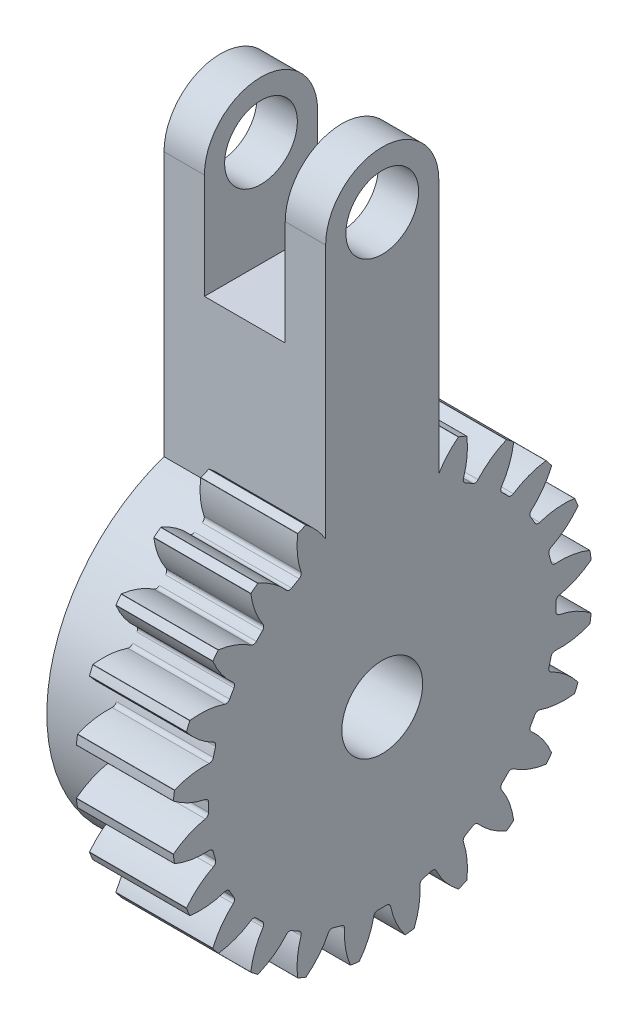
SolidWorks part; units mm, degrees
material "Nylon 101"
ref_plane "Plane1" through (0, 0, 0) normal (0, 0, 1) x (1, 0, 0)
ref_plane "Plane2" through (0, 0, 0) normal (0, 1, 0) x (1, 0, 0)
ref_plane "Plane3" through (0, 0, 0) normal (1, 0, 0) x (0, 0, -1)
sketch "HoldingSke" plane through (0, 0, 0) normal (0, 1, 0) x (1, 0, 0)
  line L0 (0, 0) -> (0.9135, -0.4067)
  line L1 (-15, 0) -> (100, 0) construction
  line L2 (0, 0) -> (-2.1039, 2.3779)
  line L3 (0, 0) -> (-11.863, 4.5341)
  line L4 (0, 0) -> (7.8894, 3.5126)
  line L5 (0, 0) -> (-46.8476, -17.4728)
  line L6 (0, 0) -> (-4.9738, -3.3558)
  line L7 (-2.1039, 2.3779) -> (8.6589, 51.2071)
  line L8 (-76.2, 54.61) -> (-75.5, 54.61)
  line L9 (-71.009, 38.7566) -> (-53.1078, 45.2721)
  line L10 (-76.2, 71.12) -> (104.1128, 71.12)
  line L11 (0, 0) -> (-6, 0)
  line L12 (-76.2, 101.6) -> (-76.162, 101.6)
  line L13 (24.9733, 27.94) -> (52.9518, 28.4284)
  line L14 (24.9733, 27.94) -> (24.9743, 27.94)
  line L15 (24.9733, 27.94) -> (100.4006, 29.5858)
  line L16 (-63.627, -1) -> (-12.827, -1)
  circle A0 centre (0, 0) radius 2
  circle A1 centre (0, 0) radius 10.749
  circle A2 centre (0, 0) radius 37.5
  circle A3 centre (0, 0) radius 2
  dimension "Num_teeth" = 24
  dimension "Pitch_radius" = 180.3128
  dimension "Width" = 6
  dimension "Thickness" = 6
sketch "BasProSke" plane through (0, 0, 0) normal (0, 1, 0) x (1, 0, 0)
  line L0 (-10, 0) -> (60, 0) construction
  line L1 (0, 0) -> (0, 13)
  line L2 (0, 0) -> (6, 0)
  line L3 (6, 0) -> (6, 13)
  line L4 (6, 13) -> (0, 13)
  dimension "Thickness" = 6
  dimension "Diameter" = 26
revolve "Base-Revolve" add sketch "BasProSke" angle 360 about L0
sketch "TooCutSke" plane through (0, 0, 0) normal (1, 0, 0) x (0, 0, -1)
  line L1 (0, 0) -> (0, 107) construction
  line L2 (0, 0) -> (-0.8513, 11.9698) construction
  line L3 (0, 0) -> (-3.127, 23.752) construction
  line L4 (-0.8513, 11.9698) -> (-1.5635, 11.876) construction
  arc A0 (0.4834, 10.7381) -> (-0.4834, 10.7381) centre (0, 0) ccw
  arc A1 (1.4409, 12.9455) -> (-1.4409, 12.9455) centre (0, 0) ccw
  circle A2 centre (0, 0) radius 12 construction
  circle A3 centre (0, 0) radius 11.2763 construction
  arc A4 (-0.4834, 10.7381) -> (-1.4409, 12.9455) centre (-5.2252, 9.9926) ccw
  arc A5 (1.4409, 12.9455) -> (0.4834, 10.7381) centre (5.2252, 9.9926) ccw
extrude "ToothCut" cut sketch "TooCutSke" along normal through all
fillet "Breaks" radius 0.02 2 edges at (3, 12.9219, -1.4227) (3, 12.9219, 1.4227) tangent propagation no
fillet "RootFillets" radius 0.251 2 edges at (3, 10.7381, -0.4834) (3, 10.7381, 0.4834)
pattern_circular "TeethCuts" count 24 over 360 about axis through (-10, 0, 0) along (1, 0, 0) of "ToothCut", "RootFillets", "Breaks"
sketch "HubNeaOneSke" plane through (0, 0, 0) normal (-1, 0, 0) x (0, 0, 1)
  circle A0 centre (0, 0) radius 10.749
  dimension "Diameter" = 21.498
extrude "HubNearOne" add sketch "HubNeaOneSke" along normal blind 4
sketch "HubNeaBotSke" plane through (0, 0, 0) normal (-1, 0, 0) x (0, 0, 1)
  circle A0 centre (0, 0) radius 10.749
  dimension "Diameter" = 21.498
extrude "HubNearBoth" add sketch "HubNeaBotSke" along normal blind 4
sketch "BorSke" plane through (0, 0, 0) normal (1, 0, 0) x (0, 0, -1)
  circle A0 centre (0, 0) radius 2.5
  dimension "Diameter" = 5
extrude "Bore" cut sketch "BorSke" along normal mid plane 100.0025
ref_plane "FarPln" through (6, 0, 0) normal (1, 0, 0) x (0, 0, -1)
sketch "HubFarSke" plane through (6, 0, 0) normal (1, 0, 0) x (0, 0, -1)
  circle A0 centre (0, 0) radius 10.749
  dimension "Diameter" = 21.498
extrude "HubFar" [suppressed] add sketch "HubFarSke" along normal blind 22.0006
sketch "Эскиз1" plane through (0, 0, 0) normal (-1, 0, 0) x (0, 0, 1)
  circle A0 centre (0, 0) radius 9
  dimension "D1" = 18
extrude "Бобышка-Вытянуть1" add sketch "Эскиз1" along normal blind 4
sketch "Эскиз2" plane through (-4, 0, 0) normal (-1, 0, 0) x (0, 0, 1)
  circle A0 centre (0, 0) radius 2.5
  dimension "D1" = 5
extrude "Вырез-Вытянуть1" cut sketch "Эскиз2" against normal through all
sketch "Эскиз3" plane through (0, 0, 0) normal (1, 0, 0) x (0, 0, -1)
  line L0 (0, 0) -> (0, 30) construction
  line L1 (-3.5, 26.5) -> (-3.5, 7)
  line L2 (3.5, 26.5) -> (3.5, 7)
  line L4 (3.5, 7) -> (-3.5, 7)
  arc A0 (-3.5, 26.5) -> (3.5, 26.5) centre (0, 26.5) cw
  dimension "D4" = 7
  dimension "D3" = 3.5
  dimension "D1" = 30
  dimension "D2" = 26.5
extrude "Бобышка-Вытянуть2" add sketch "Эскиз3" along normal blind 6 and the other way blind 4
sketch "Эскиз4" plane through (0, 0, 0) normal (0, 0, 1) x (1, 0, 0)
  line L0 (-1.5, 32) -> (3.5, 32)
  line L1 (-1.5, 32) -> (-1.5, 20)
  line L2 (-1.5, 20) -> (3.5, 20)
  line L3 (3.5, 32) -> (3.5, 20)
  line L4 (0, 10.749) -> (0, -10.749) construction
  line L5 (-4, 30) -> (-4, 26.5) construction
  point P6 (0, 0)
  dimension "D1" = 12
  dimension "D2" = 5
  dimension "D3" = 20
  dimension "D4" = 2.5
extrude "Вырез-Вытянуть2" cut sketch "Эскиз4" against normal through all both and the other way through all
hole_wizard "Отверстие с зазором M41" positions "Эскиз7" profile "Эскиз6" hole size "M4" standard "JIS"
sketch "Эскиз7" plane through (6, 0, 0) normal (1, 0, 0) x (0, 0, -1)
  line L0 (3.5, 10.74) -> (3.5, 26.5) construction
  arc A1 (3.5, 26.5) -> (-3.5, 26.5) centre (0, 26.5) ccw construction
  point P0 (0, 26.5)
  point P17 (0, 30)
  dimension "D1" = 3.5
  dimension "D2" = 3.5
sketch "Эскиз6" plane through (6, 26.5, 0) normal (0, 1, 0) x (0, 0, -1)
  line L0 (0, 0) -> (0, 16.3519)
  line L1 (0, 16.3519) -> (2.25, 15)
  line L2 (2.25, 15) -> (2.25, 0)
  line L5 (2.25, 0) -> (0, 0)
  line L10 (0, 16.3519) -> (-2.25, 15) construction
  line L11 (0, -6.35) -> (0, 107.95) construction
  dimension "Диаметр отверстия" = 4.5
  dimension "Глубина отверстия" = 15
  dimension "Угол заточки сверла" = 118
equation "' \"Module@HoldingSke\" = 6.35"
equation "' \"Num_teeth@HoldingSke\" = 12"
equation "' \"Ap@HoldingSke\" =  20"
equation "' \"Ap@HoldingSke\" = 20"
equation "' \"Width@HoldingSke\" = 0.5 * 25.4"
equation "' \"Hub_dia@HoldingSke\"= 1 * 25.4"
equation "' \"Hub_dia@HoldingSke\" = 1 * 25.4"
equation "' \"Overall_len@HoldingSke\" = 1.0 * 25.4"
equation "' \"Bore@HoldingSke\" = 0.75 * 25.4"
equation "' \"T_dim@HoldingSke\" = 0.1 * 25.4"
equation "' \"Width@KeySke\" = 0.25 * 25.4"
equation "' \"Show_teeth@HoldingSke\" = 13"
equation "' \"Backlash@HoldingSke\" = 0.009 * 25.4"
equation "' \"Addendum_fac@HoldingSke\" = 1.0"
equation "' \"Dedendum_fac@HoldingSke\" = 1.25"
equation "' \"Dedendum_add@HoldingSke\" = 0.00005 * 25.4"
equation "' \"Clearance_fac@HoldingSke\" = 0.25"
equation "\"Pitch@HoldingSke\" = 1 / \"Module@HoldingSke\""
equation "\"Overcut_dia@TooCutSke\" = (\"Num_teeth@HoldingSke\" + 2 * \"Addendum_fac@HoldingSke\") / \"Pitch@HoldingSke\" + 0.002 * 25.4"
equation "\"Pitch_dia@TooCutSke\" = \"Num_teeth@HoldingSke\" / \"Pitch@HoldingSke\""
equation "\"Base_dia@TooCutSke\" = \"Num_teeth@HoldingSke\" / \"Pitch@HoldingSke\" * cos((\"Ap@HoldingSke\"  * 3.14159265 / 180))"
equation "\"Root_dia@TooCutSke\" = (\"Num_teeth@HoldingSke\" + 2) / \"Pitch@HoldingSke\" - 2 * (\"Addendum_fac@HoldingSke\" + \"Dedendum_fac@HoldingSke\") / \"Pitch@HoldingSke\" - \"Dedendum_add@HoldingSke\" * 2"
equation "\"Half_ang@TooCutSke\" = 180 / \"Num_teeth@HoldingSke\""
equation "\"Half_CT@TooCutSke\" = \"Num_teeth@HoldingSke\" / \"Pitch@HoldingSke\" * sin((3.14159265 / 2 / \"Num_teeth@HoldingSke\")) / 2 - 7 * \"Backlash@HoldingSke\" / 4"
equation "\"Flank_rad@TooCutSke\" = \"Num_teeth@HoldingSke\" / \"Pitch@HoldingSke\" / 5"
equation "\"Radius@RootFillets\" = \"Clearance_fac@HoldingSke\" / \"Pitch@HoldingSke\" + \"Dedendum_add@HoldingSke\""
equation "\"Break_rad@Breaks\" = 0.02 / \"Pitch@HoldingSke\""
equation "\"Thickness@HoldingSke\" = \"Width@HoldingSke\""
equation "\"OAL@HoldingSke\" = \"Thickness@HoldingSke\""
equation "\"MHD@HoldingSke\" = (\"Num_teeth@HoldingSke\" + 2) / \"Pitch@HoldingSke\" - 2 * (\"Addendum_fac@HoldingSke\" + \"Dedendum_fac@HoldingSke\")  / \"Pitch@HoldingSke\" - \"Dedendum_add@HoldingSke\" * 2"
equation "\"MBD@HoldingSke\" = (\"Num_teeth@HoldingSke\" + 2) / \"Pitch@HoldingSke\" - 2 * (\"Addendum_fac@HoldingSke\" + \"Dedendum_fac@HoldingSke\")  / \"Pitch@HoldingSke\" - \"Dedendum_add@HoldingSke\" * 2 - 0.002 * 25.4"
equation "\"MHD@HoldingSke\" = ((sgn( \"MHD@HoldingSke\" - \"Hub_dia@HoldingSke\" )-1)*( \"MHD@HoldingSke\" - \"Hub_dia@HoldingSke\" ))/-2+ \"Hub_dia@HoldingSke\""
equation "\"MBD@HoldingSke\" = ((sgn( \"MBD@HoldingSke\" - \"Bore@HoldingSke\" )-1)*( \"MBD@HoldingSke\" - \"Bore@HoldingSke\" ))/-2+ \"Bore@HoldingSke\""
equation "\"OAL@HoldingSke\" = ((sgn( \"OAL@HoldingSke\" - \"Overall_len@HoldingSke\" )+1)*( \"OAL@HoldingSke\" - \"Overall_len@HoldingSke\" ))/2 + \"Overall_len@HoldingSke\" + 0.000002 * 25.4"
equation "\"Num_teeth@TeethCuts\" = int( \"Show_teeth@HoldingSke\" ) + 1"
equation "\"Num_teeth@TeethCuts\" = ((sgn( \"Num_teeth@TeethCuts\" - \"Num_teeth@HoldingSke\" )-1)*( \"Num_teeth@TeethCuts\" - \"Num_teeth@HoldingSke\" ))/-2+ \"Num_teeth@HoldingSke\""
equation "\"Num_teeth@TeethCuts\" = ((sgn( \"Num_teeth@TeethCuts\" - 2.0)+1)*( \"Num_teeth@TeethCuts\" - 2.0))/2 +2.0"
equation "\"Angle@TeethCuts\" = 360.0 / \"Num_teeth@HoldingSke\""
equation "\"Diameter@BasProSke\" = (\"Num_teeth@HoldingSke\" + 2 * \"Addendum_fac@HoldingSke\") / \"Pitch@HoldingSke\""
equation "\"Thickness@BasProSke\"  = \"Thickness@HoldingSke\""
equation "' \"Fillet_rad@BasProSke\" =  \"Thickness@HoldingSke\" * 0.05"
equation "' \"Fillet_rad@BasProSke\" = \"Thickness@HoldingSke\" * 0.05"
equation "\"MHD@HoldingSke\" = ((sgn( \"MHD@HoldingSke\" - \"Root_dia@TooCutSke\" )-1)*( \"MHD@HoldingSke\" - \"Root_dia@TooCutSke\" ))/-2+ \"Root_dia@TooCutSke\""
equation "\"Diameter@HubNeaOneSke\" = \"MHD@HoldingSke\""
equation "\"Diameter@HubNeaBotSke\" = \"MHD@HoldingSke\""
equation "\"Thickness@FarPln\" = \"Thickness@BasProSke\""
equation "\"Diameter@HubFarSke\" = \"MHD@HoldingSke\""
equation "\"Length@HubFar\" = ( \"OAL@HoldingSke\" - \"Thickness@BasProSke\" ) / 2.0"
equation "\"D1@Bore\" = \"OAL@HoldingSke\" * 2.0"
